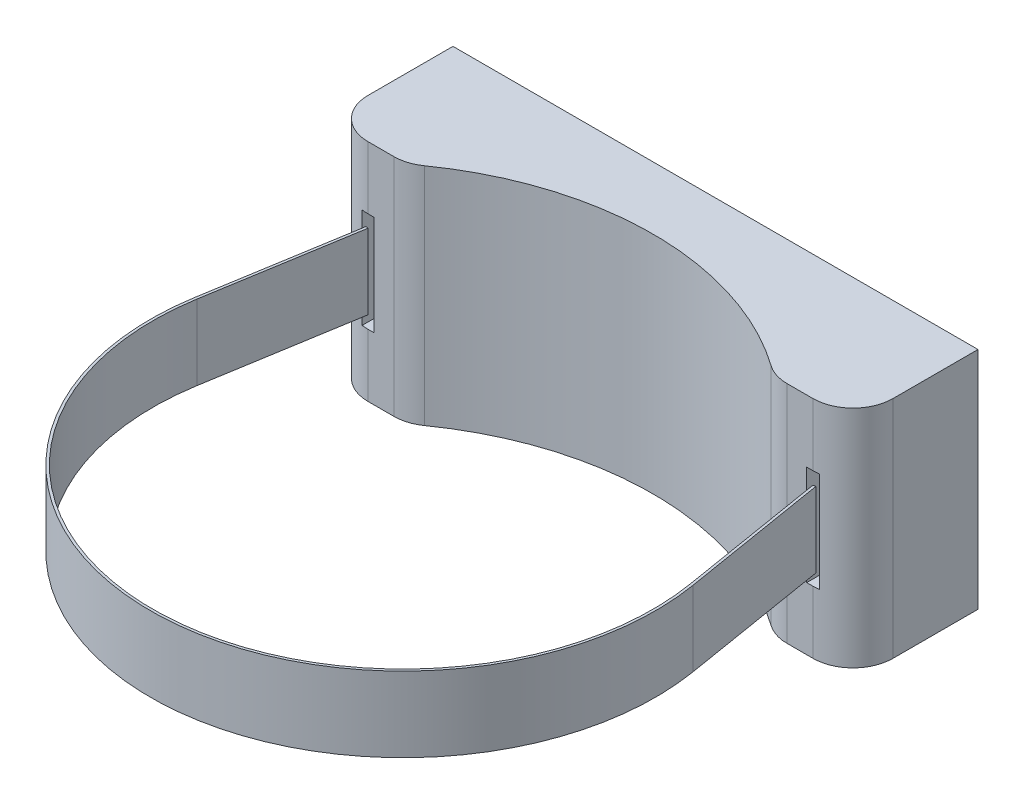
SolidWorks part; units mm, degrees
material "PPE"
ref_plane "Front" through (0, 0, 0) normal (0, 0, 1) x (1, 0, 0)
ref_plane "Top" through (0, 0, 0) normal (0, 1, 0) x (1, 0, 0)
ref_plane "Right" through (0, 0, 0) normal (1, 0, 0) x (0, 0, -1)
sketch "Sketch1" plane through (0, 0, 0) normal (0, 1, 0) x (1, 0, 0)
  line L0 (0, 0) -> (0, -152.4) construction
  line L1 (-133.35, 31.75) -> (133.35, 31.75)
  line L2 (-133.35, 31.75) -> (-133.35, -31.75)
  line L3 (-133.35, -31.75) -> (-93.1093, -31.75)
  line L4 (133.35, 31.75) -> (133.35, -31.75)
  line L5 (-133.35, 31.75) -> (133.35, -31.75) construction
  line L6 (-133.35, -31.75) -> (133.35, 31.75) construction
  line L7 (93.1093, -31.75) -> (133.35, -31.75)
  arc A0 (93.1093, -31.75) -> (-93.1093, -31.75) centre (0, -152.4) ccw
  point P0 (0, 0)
  dimension "D3" = 304.8
  dimension "D1" = 266.7
  dimension "D2" = 63.5
  dimension "D4" = 152.4
extrude "Boss-Extrude1" add sketch "Sketch1" along normal blind 114.3
fillet "Fillet1" radius 20.32 2 edges at (133.35, 57.15, 31.75) (-133.35, 57.15, 31.75)
fillet "Fillet2" radius 20.32 2 edges at (93.1093, 57.15, 31.75) (-93.1093, 57.15, 31.75)
sketch "Sketch2" plane through (0, 0, 31.75) normal (0, 0, 1) x (1, 0, 0)
  line L0 (-113.03, 114.3) -> (-113.03, 0) construction
  line L1 (-116.205, 82.55) -> (-109.855, 82.55)
  line L2 (-116.205, 82.55) -> (-116.205, 31.75)
  line L3 (-116.205, 31.75) -> (-109.855, 31.75)
  line L4 (-109.855, 82.55) -> (-109.855, 31.75)
  line L5 (-116.205, 82.55) -> (-109.855, 31.75) construction
  line L6 (-116.205, 31.75) -> (-109.855, 82.55) construction
  line L7 (113.03, 0) -> (113.03, 114.3) construction
  line L8 (109.855, 82.55) -> (116.205, 82.55)
  line L9 (109.855, 82.55) -> (109.855, 31.75)
  line L10 (109.855, 31.75) -> (116.205, 31.75)
  line L11 (116.205, 82.55) -> (116.205, 31.75)
  line L12 (109.855, 82.55) -> (116.205, 31.75) construction
  line L13 (109.855, 31.75) -> (116.205, 82.55) construction
  point P0 (-113.03, 57.15)
  point P7 (113.03, 57.15)
  dimension "D1" = 50.8
  dimension "D2" = 6.35
extrude "Cut-Extrude1" cut sketch "Sketch2" against normal through all
sketch "Sketch3" plane through (0, 31.75, 0) normal (0, 1, 0) x (1, 0, 0)
  line L0 (0, 0) -> (0, -127) construction
  line L1 (-113.03, -31.75) -> (-125.3136, -106.3721)
  line L2 (113.03, -31.75) -> (125.3136, -106.3721)
  arc A0 (-125.3136, -106.3721) -> (125.3136, -106.3721) centre (0, -127) ccw
  point P11 (-113.03, -31.75)
  point P12 (-117.5954, -79.0383)
  point P13 (118.5006, -81.3206)
  dimension "D1" = 254
  dimension "D2" = 127
extrude "Extrude-Thin1" add sketch "Sketch3" along normal blind 38.1 from offset 6.35 separate body thin thin type one direction wall 1.27
